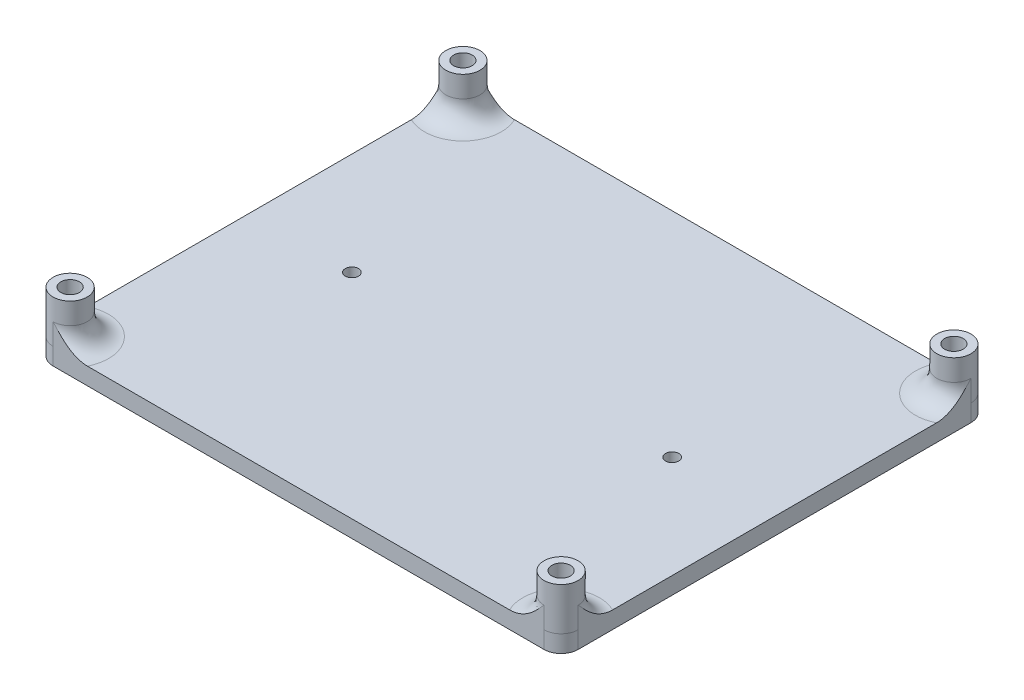
SolidWorks part; units mm, degrees
ref_plane "Alzado" through (0, 0, 0) normal (0, 0, 1) x (1, 0, 0)
ref_plane "Planta" through (0, 0, 0) normal (0, 1, 0) x (1, 0, 0)
ref_plane "Vista lateral" through (0, 0, 0) normal (1, 0, 0) x (0, 0, -1)
sketch "Croquis1" plane through (0, 0, 0) normal (0, 1, 0) x (1, 0, 0)
  line L1 (0, 0) -> (123, 0)
  line L2 (0, 0) -> (0, 100)
  line L3 (0, 100) -> (123, 100)
  line L4 (123, 0) -> (123, 100)
  dimension "D1" = 123
  dimension "D2" = 100
extrude "Saliente-Extruir1" add sketch "Croquis1" along normal blind 4
sketch "Croquis2" plane through (0, 4, 0) normal (0, 1, 0) x (1, 0, 0)
  line L0 (61.5, 100) -> (61.5, 0) construction
  line L1 (123, 100) -> (0, 100) construction
  line L2 (0, 0) -> (123, 0) construction
  line L3 (123, 0) -> (123, 100) construction
  line L4 (4, 4) -> (119, 4) construction
  line L5 (4, 4) -> (4, 96) construction
  line L6 (4, 96) -> (119, 96) construction
  line L7 (119, 4) -> (119, 96) construction
  line L8 (4, 4) -> (119, 96) construction
  line L9 (4, 96) -> (119, 4) construction
  circle A0 centre (4, 96) radius 4
  circle A1 centre (4, 4) radius 4
  circle A2 centre (119, 4) radius 4
  circle A3 centre (119, 96) radius 4
  point P6 (61.5, 50)
  dimension "D1" = 115
  dimension "D2" = 92
extrude "Saliente-Extruir2" add sketch "Croquis2" along normal blind 10
sketch "Croquis3" plane through (0, 14, 0) normal (0, 1, 0) x (1, 0, 0)
  circle A0 centre (4, 4) radius 4 construction
  circle A1 centre (4, 96) radius 4
  circle A2 centre (4, 96) radius 4
  arc A3 (123, 4) -> (119, 0) centre (119, 4) ccw construction
  arc A4 (119, 100) -> (123, 96) centre (119, 96) ccw construction
  circle A5 centre (4, 4) radius 4
  arc A6 (123, 4) -> (119, 0) centre (119, 4) ccw
  arc A7 (119, 100) -> (123, 96) centre (119, 96) ccw
  circle A8 centre (4, 96) radius 2.175
  circle A9 centre (119, 96) radius 2.175
  circle A10 centre (119, 4) radius 2.175
  circle A11 centre (4, 4) radius 2.175
  dimension "D2" = 4.35
  dimension "D1" = 0
extrude "Cortar-Extruir1" cut sketch "Croquis3" against normal blind 4.5 contours A8 | A9 | A10 | A11 region at (4, 14, -96) region at (119, 14, -96) region at (119, 14, -4) region at (4, 14, -4)
fillet "Redondeo1" radius 4 4 edges at (0, 2, -100) (123, 2, -100) (123, 2, 0) (0, 2, 0)
fillet "Redondeo2" radius 5 4 edges at (116.1716, 4, -6.8284) (116.1716, 4, -93.1716) (6.8284, 4, -93.1716) (6.8284, 4, -6.8284)
sketch "Croquis4" plane through (0, 4, 0) normal (0, 1, 0) x (1, 0, 0)
  line L0 (0, 50) -> (123, 50) construction
  line L1 (0, 87.9377) -> (0, 12.0623) construction
  line L2 (123, 12.0623) -> (123, 87.9377) construction
  circle A0 centre (24, 50) radius 1.55
  circle A1 centre (99, 50) radius 1.55
  dimension "D2" = 3.1
  dimension "D1" = 75
  dimension "D3" = 24
extrude "Cortar-Extruir2" cut sketch "Croquis4" against normal up to surface (4 mm away) up to face at (61.5, 0, -50)
